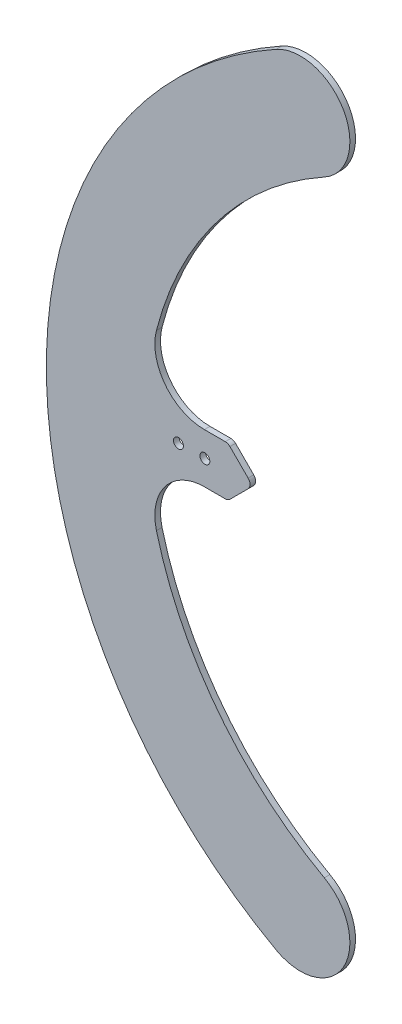
SolidWorks part; units mm, degrees
ref_plane "Front Plane" through (0, 0, 0) normal (0, 0, 1) x (1, 0, 0)
ref_plane "Top Plane" through (0, 0, 0) normal (0, 1, 0) x (1, 0, 0)
ref_plane "Right Plane" through (0, 0, 0) normal (1, 0, 0) x (0, 0, -1)
sketch "Sketch1" plane through (0, 0, 0) normal (0, 0, 1) x (1, 0, 0)
  line L0 (-32.8019, 0) -> (18.2589, 0) construction
  line L1 (72.5, 105) -> (72.5, 135) construction
  line L2 (207.5, -120) -> (-62.5, -120)
  line L3 (207.5, -120) -> (207.5, 120)
  line L4 (207.5, 120) -> (-62.5, 120)
  line L5 (-27.5, 6) -> (-27.5, -6)
  line L6 (-26, -7.5) -> (-7.5, -7.5)
  line L7 (-7.5, -7.5) -> (0, 0)
  line L8 (0, 0) -> (-7.5, 7.5)
  line L9 (-7.5, 7.5) -> (-26, 7.5)
  line L10 (-27.5, 6) -> (-27.5, -6)
  line L11 (-26, -7.5) -> (-7.5, -7.5)
  line L12 (-7.5, -7.5) -> (0, 0)
  line L13 (0, 0) -> (-7.5, 7.5)
  line L14 (-7.5, 7.5) -> (-26, 7.5)
  line L15 (-62.5, -120) -> (-62.5, 120)
  line L16 (207.5, -120) -> (-62.5, 120) construction
  line L17 (207.5, 120) -> (-62.5, -120) construction
  line L18 (-26, 7.5) -> (-32.2318, 7.5)
  line L19 (-26, -7.5) -> (-32.2318, -7.5)
  circle A0 centre (-22.5, 0) radius 1.5 construction
  circle A1 centre (-14.5, 0) radius 1.5 construction
  arc A2 (-27.5, -6) -> (-26, -7.5) centre (-26, -6) ccw
  arc A3 (-26, 7.5) -> (-27.5, 6) centre (-26, 6) ccw
  arc A4 (-27.5, -6) -> (-26, -7.5) centre (-26, -6) ccw
  arc A5 (-26, 7.5) -> (-27.5, 6) centre (-26, 6) ccw
  circle A6 centre (-22.5, 0) radius 1.5
  circle A7 centre (-14.5, 0) radius 1.5
  circle A8 centre (72.5, 0) radius 135
  circle A9 centre (72.5, 0) radius 105
  circle A10 centre (72.5, 0) radius 120
  circle A11 centre (14.4052, 105) radius 15
  circle A12 centre (14.4052, -105) radius 15
  point P19 (-62.5, 0)
  point P27 (72.5, 120)
  dimension "D3" = 270
  dimension "D5" = 30
  dimension "D2" = 55
  dimension "D4" = 240
  dimension "D1" = 0
extrude "Boss-Extrude1" add sketch "Sketch1" along normal blind 1.7 contours L14 A5 L10 A4 L11 L12 L13 A7 A6 | L18 A9 L19 A4 L10 A5 | A10 A12 A9 A11 | A8 A12 A10 A11 | A10 A11 | A10 A11 | A12 A10 | A12 A10 region at (11.4064, -110.4201, 0) region at (17.5676, -99.2844, 0) region at (-41.6713, -67.3124, 0) region at (-45.4417, 0, 0) region at (11.4064, 110.4201, 0) region at (17.5676, 99.2844, 0) region at (-29.9199, 0, 0) region at (-26.8392, -6.8392, 0)
fillet "Fillet1" radius 15 2 edges at (-32.2318, -7.5, 0.85) (-32.2318, 7.5, 0.85)
fillet "Fillet2" radius 2 3 edges at (-7.5, -7.5, 0.85) (-7.5, 7.5, 0.85) (0, 0, 0.85)
